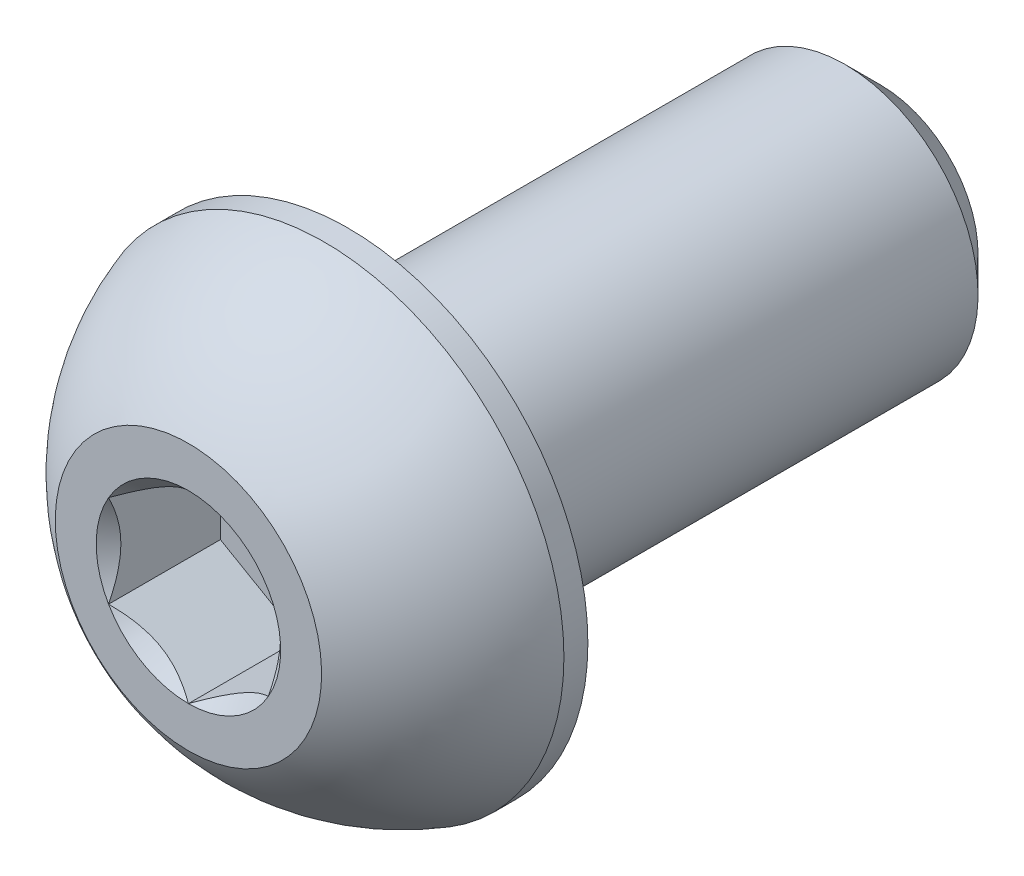
SolidWorks part; units mm, degrees
ref_plane "Front" through (0, 0, 0) normal (0, 0, 1) x (1, 0, 0)
ref_plane "Top" through (0, 0, 0) normal (0, 1, 0) x (1, 0, 0)
ref_plane "Right" through (0, 0, 0) normal (1, 0, 0) x (0, 0, -1)
sketch "Sketch1" plane through (0, 0, 0) normal (1, 0, 0) x (0, 0, -1)
  line L2 (1.5, 1.25) -> (6.5, 1.25)
  line L3 (6.5, 1.25) -> (6.5, 0)
  line L4 (6.5, 0) -> (1.5, 0)
  line L6 (1.275, 2.25) -> (1.5, 2.25) construction
  line L7 (6.5, 1.25) -> (6.5, -1.25) construction
  line L8 (0, 0) -> (1.5, 0) construction
  line L9 (1.5, 2.25) -> (1.5, -2.25) construction
  line L11 (1.5, 1.25) -> (1.5, 0)
  line L13 (0, 0.75) -> (0, -0.75) construction
  line L14 (0, 0.75) -> (0, 1.25) construction
  arc A3 (0, 1.25) -> (1.275, 2.25) centre (2.01, 0) cw construction
  dimension "D1" = 0.225
revolve "Revolve1" add sketch "Sketch1" angle 360 mid plane about L4
sketch "Sketch3" plane through (0, 0, -6.5) normal (0, 0, -1) x (-1, 0, 0)
  circle A0 centre (0, 0) radius 1.25
curve "Helix/Spiral1" pitch 0.45 height 5.45 turns 12.1111
chamfer "Chamfer1" distance 0.3375 angle 45 1 edges at (0, 1.25, -6.5)
sketch "Sketch7" plane through (0, 0, 0) normal (1, 0, 0) x (0, 0, -1)
  line L6 (1.275, 2.25) -> (1.5, 2.25) construction
  line L8 (0, 0) -> (1.5, 0) construction
  line L11 (1.5, 2.25) -> (1.5, -2.25) construction
  line L12 (1.275, 2.25) -> (1.5, 2.25)
  line L13 (0, 0) -> (1.5, 0)
  line L14 (0, 0.75) -> (0, -0.75) construction
  line L15 (1.5, 2.25) -> (1.5, 0)
  line L16 (0, 1.25) -> (0, 0)
  arc A2 (1.275, 2.25) -> (0, 1.25) centre (2.01, 0) ccw construction
  arc A3 (1.275, 2.25) -> (0, 1.25) centre (2.01, 0) ccw
revolve "Revolve2" add sketch "Sketch7" angle 360 mid plane about L13
sketch "Sketch5" plane through (0, 0, 0) normal (0, 0, 1) x (1, 0, 0)
  line L1 (0.75, -0.433) -> (0.75, 0.433)
  line L2 (0.75, 0.433) -> (0, 0.866)
  line L3 (0, 0.866) -> (-0.75, 0.433)
  line L4 (-0.75, 0.433) -> (-0.75, -0.433)
  line L5 (-0.75, -0.433) -> (0, -0.866)
  line L6 (0, -0.866) -> (0.75, -0.433)
  circle A0 centre (0, 0) radius 0.75 construction
extrude "Cut-Extrude2" cut sketch "Sketch5" against normal blind 1.05
sketch "Sketch6" plane through (0, 0, 0) normal (0, 0, 1) x (1, 0, 0)
  circle A0 centre (0, 0) radius 0.866
extrude "Cut-Extrude3" cut sketch "Sketch6" against normal blind 1.05 draft 45
sketch "Sketch2" [suppressed] plane through (0, 0, 0) normal (1, 0, 0) x (0, 0, -1)
  line L0 (9.1625, 1.25) -> (9.5563, 1.25)
  line L1 (9.5563, 1.25) -> (9.3875, 0.9577)
  line L2 (9.3875, 0.9577) -> (9.3313, 0.9577)
  line L3 (9.3313, 0.9577) -> (9.1625, 1.25)
  line L4 (9.2469, 1.1039) -> (9.4719, 1.1039) construction
  dimension "D1" = 60
  dimension "D2" = 0.0563
  dimension "D3" = 0.225
sweep "Cut-Sweep1" [suppressed] cut profiles "Sketch2" path "Helix/Spiral1"
sketch "Sketch10" [suppressed] plane through (0, 0, 0) normal (1, 0, 0) x (0, 0, -1)
  line L0 (9.5, 1.25) -> (9.5, -1.25) construction
  point P0 (8.825, -1.25)
  dimension "D1" = 0.675
ref_axis "Center Axis 1" through (0, 0, -8.1113) along (0, 0, 1)
ref_plane "Contact Plane 1" through (0, 0, -1.5) normal (0, 0, -1) x (-1, 0, 0)
ref_plane "Contact Plane 2" through (0, 0, 0) normal (0, 0, 1) x (1, 0, 0)
equation "\"D3@Helix/Spiral1\" = \"Lg@Sketch1\" + \"D4@Helix/Spiral1\""
equation "\"D2@Sketch2\" = \"D4@Helix/Spiral1\" * .125"
equation "\"D3@Sketch2\" = \"D4@Helix/Spiral1\" * .5"
equation "\"D1@Chamfer1\" = \"D4@Helix/Spiral1\" * .75"
equation "\"D1@Cut-Extrude2\" = \"Head Ht@Sketch1\" * .7"
equation "\"D1@Sketch1\" = \"Head Ht@Sketch1\" * .15"
equation "\"D1@Sketch10\" = \"D4@Helix/Spiral1\" * 1.5"
equation "\"D1@Cut-Extrude3\" = \"D1@Cut-Extrude2\""
